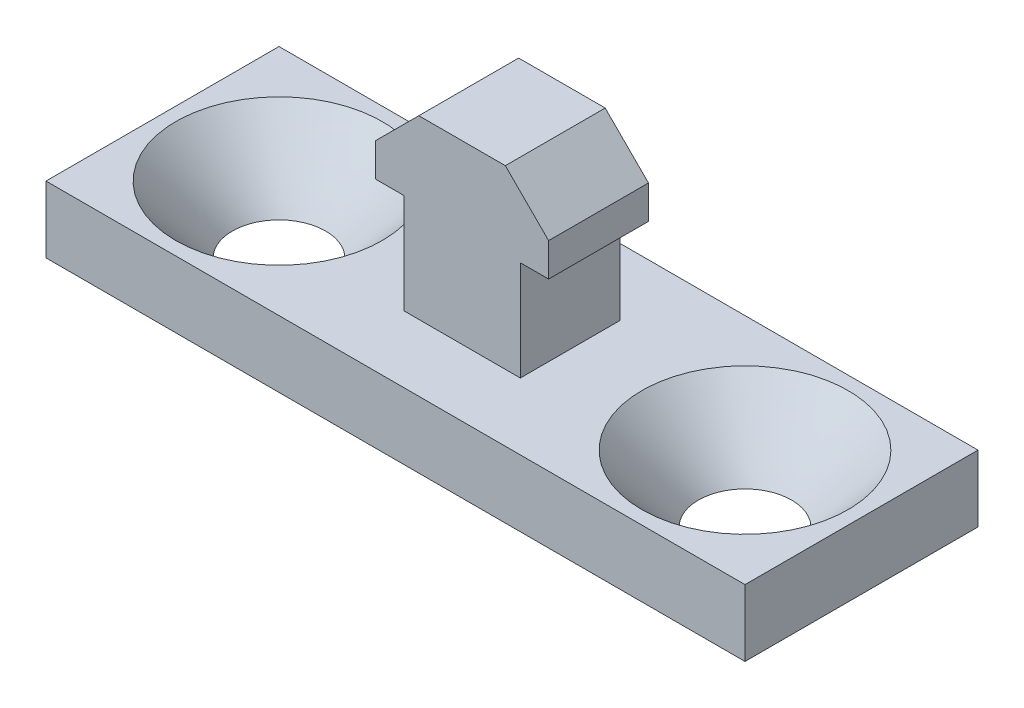
SolidWorks part; units mm, degrees
ref_plane "Front Plane" through (0, 0, 0) normal (0, 0, 1) x (1, 0, 0)
ref_plane "Top Plane" through (0, 0, 0) normal (0, 1, 0) x (1, 0, 0)
ref_plane "Right Plane" through (0, 0, 0) normal (1, 0, 0) x (0, 0, -1)
sketch "Sketch1" plane through (0, 0, 0) normal (0, 1, 0) x (1, 0, 0)
  line L1 (-10.5, -3.5) -> (10.5, -3.5)
  line L2 (-10.5, -3.5) -> (-10.5, 3.5)
  line L3 (-10.5, 3.5) -> (10.5, 3.5)
  line L4 (10.5, -3.5) -> (10.5, 3.5)
  line L5 (-10.5, -3.5) -> (10.5, 3.5) construction
  line L6 (-10.5, 3.5) -> (10.5, -3.5) construction
  point P0 (0, 0)
  dimension "D1" = 21
  dimension "D2" = 7
extrude "Boss-Extrude1" add sketch "Sketch1" along normal blind 2
sketch "Sketch2" plane through (0, 2, 0) normal (0, 1, 0) x (1, 0, 0)
  line L0 (-7, 0) -> (7, 0) construction
  circle A0 centre (-7, 0) radius 3.1
  circle A1 centre (7, 0) radius 3.1
  point P4 (0, 0)
  dimension "D2" = 6.2
  dimension "D1" = 14
sketch "Sketch3" plane through (0, 0, 0) normal (0, -1, 0) x (1, 0, 0)
  circle A0 centre (-7, 0) radius 1.4
  circle A1 centre (7, 0) radius 1.4
  dimension "D1" = 2.8
loft "Cut-Loft1" cut section "Sketch2" section "Sketch3" connector at (-8.8111, 2, 2.5159) connector at (-7.2216, 0, 1.3823)
mirror "Mirror1" about plane through (0, 0, 0) normal (1, 0, 0) of "Cut-Loft1"
sketch "Sketch4" plane through (0, 2, 0) normal (0, 1, 0) x (1, 0, 0)
  line L1 (-1.75, -1.5) -> (1.75, -1.5)
  line L2 (-1.75, -1.5) -> (-1.75, 1.5)
  line L3 (-1.75, 1.5) -> (1.75, 1.5)
  line L4 (1.75, -1.5) -> (1.75, 1.5)
  line L5 (-1.75, -1.5) -> (1.75, 1.5) construction
  line L6 (-1.75, 1.5) -> (1.75, -1.5) construction
  point P0 (0, 0)
  dimension "D1" = 3.5
  dimension "D2" = 3
extrude "Boss-Extrude2" add sketch "Sketch4" along normal blind 3
sketch "Sketch5" plane through (0, 0, 0) normal (0, 0, 1) x (1, 0, 0)
  line L0 (0, -994.9181) -> (0, 49005.0819) construction
  line L1 (-2.6, 5) -> (-2.6, 6)
  line L2 (-2.6, 5) -> (2.6, 5)
  line L3 (-2.6, 6) -> (-1.3, 7.3)
  line L4 (-1.3, 7.3) -> (1.3, 7.3)
  line L5 (2.6, 5) -> (2.6, 6)
  line L6 (2.6, 6) -> (1.3, 7.3)
  line L7 (0, -2.7501) -> (0, 2.7501) construction
  line L8 (-1.75, 5) -> (1.75, 5) construction
  point P5 (0, 5)
  point P8 (0, 7.3)
  dimension "D1" = 1
  dimension "D2" = 2.3
  dimension "D3" = 5.2
  dimension "D4" = 2.6
extrude "Boss-Extrude3" add sketch "Sketch5" along normal up to surface and the other way up to surface up to face at (0, 3.5, 1.5) other way up to face at (0, 3.5, -1.5)
